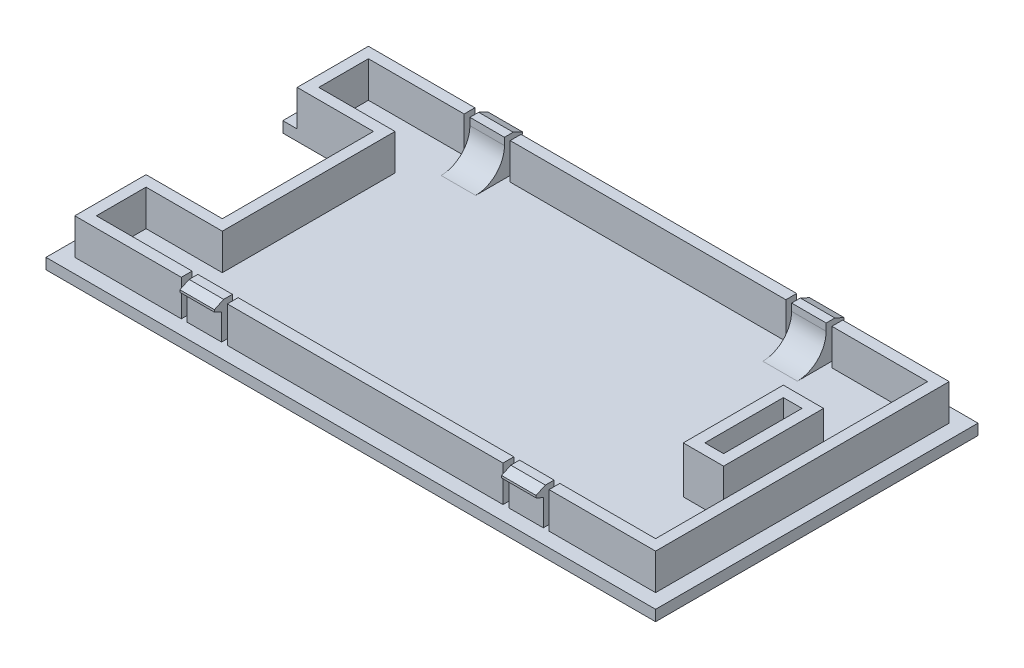
SolidWorks part; units mm, degrees
ref_plane "Front Plane" through (0, 0, 0) normal (0, 0, 1) x (1, 0, 0)
ref_plane "Top Plane" through (0, 0, 0) normal (0, 1, 0) x (1, 0, 0)
ref_plane "Right Plane" through (0, 0, 0) normal (1, 0, 0) x (0, 0, -1)
sketch "Sketch1" plane through (0, 0, 0) normal (0, 1, 0) x (1, 0, 0)
  line L0 (-42.35, 10.5) -> (-29.75, 10.5)
  line L1 (-42.35, -22.4) -> (42.35, -22.4)
  line L2 (-42.35, -22.4) -> (-42.35, -10.5)
  line L3 (-42.35, 22.4) -> (42.35, 22.4)
  line L4 (42.35, -22.4) -> (42.35, 22.4)
  line L5 (-42.35, -22.4) -> (42.35, 22.4) construction
  line L6 (-42.35, 22.4) -> (42.35, -22.4) construction
  line L7 (-29.75, 10.5) -> (-29.75, -10.5)
  line L8 (-29.75, -10.5) -> (-42.35, -10.5)
  line L9 (-42.35, 10.5) -> (-42.35, 22.4)
  point P0 (0, 0)
  dimension "D1" = 84.7
  dimension "D2" = 44.8
  dimension "D3" = 10.5
  dimension "D4" = 10.5
  dimension "D5" = 12.6
extrude "Boss-Extrude1" add sketch "Sketch1" along normal blind 2
sketch "Sketch2" plane through (0, 2, 0) normal (0, 1, 0) x (1, 0, 0)
  line L5 (-38.85, -12) -> (-38.85, -18.9)
  line L6 (-38.85, -18.9) -> (38.85, -18.9)
  line L7 (38.85, -18.9) -> (38.85, 18.9)
  line L8 (38.85, 18.9) -> (-38.85, 18.9)
  line L9 (-38.85, 18.9) -> (-38.85, 12)
  line L10 (-40.35, 20.4) -> (-40.35, 10.5)
  line L11 (-40.35, -10.5) -> (-40.35, -20.4)
  line L12 (-40.35, -20.4) -> (40.35, -20.4)
  line L13 (40.35, -20.4) -> (40.35, 20.4)
  line L14 (40.35, 20.4) -> (-40.35, 20.4)
  line L15 (-40.35, 20.4) -> (-40.35, 10.5)
  line L16 (-40.35, -10.5) -> (-40.35, -20.4)
  line L17 (-40.35, -20.4) -> (40.35, -20.4)
  line L18 (40.35, -20.4) -> (40.35, 20.4)
  line L19 (40.35, 20.4) -> (-40.35, 20.4)
  line L20 (-40.35, 10.5) -> (-29.75, 10.5)
  line L21 (-29.75, 10.5) -> (-29.75, -10.5)
  line L22 (-29.75, -10.5) -> (-40.35, -10.5)
  line L23 (-38.85, 12) -> (-28.25, 12)
  line L24 (-28.25, 12) -> (-28.25, -12)
  line L25 (-28.25, -12) -> (-38.85, -12)
  line L26 (-38.85, 18.9) -> (-38.85, 10.5) construction
  line L27 (-38.85, -10.5) -> (-38.85, -18.9) construction
  dimension "D3" = 1.5
  dimension "D4" = 1.5
  dimension "D5" = 1.5
  dimension "D1" = 2
  dimension "D2" = 1.5
extrude "Boss-Extrude2" add sketch "Sketch2" along normal blind 5
sketch "Sketch3" plane through (0, 7, 0) normal (0, 1, 0) x (1, 0, 0)
  line L0 (0, 22.4) -> (0, -22.4) construction
  line L1 (42.35, 22.4) -> (-42.35, 22.4) construction
  line L2 (-42.35, -22.4) -> (42.35, -22.4) construction
  line L3 (40.35, 20.4) -> (-40.35, 20.4) construction
  line L4 (-24.75, 20.4) -> (-25.55, 20.4)
  line L5 (-24.75, 20.4) -> (-24.75, 18.9)
  line L6 (-24.75, 18.9) -> (-25.55, 18.9)
  line L7 (-25.55, 20.4) -> (-25.55, 18.9)
  line L8 (38.85, 18.9) -> (-38.85, 18.9) construction
  line L10 (-19.95, 20.4) -> (-19.15, 20.4)
  line L11 (-19.95, 20.4) -> (-19.95, 18.9)
  line L12 (-19.95, 18.9) -> (-19.15, 18.9)
  line L13 (-19.15, 20.4) -> (-19.15, 18.9)
  line L14 (-29.75, 0) -> (0, 0) construction
  line L15 (-29.75, 10.5) -> (-29.75, -10.5) construction
  line L16 (-19.15, -20.4) -> (-19.15, -18.9)
  line L17 (-19.95, -18.9) -> (-19.15, -18.9)
  line L18 (-19.95, -20.4) -> (-19.95, -18.9)
  line L19 (-19.95, -20.4) -> (-19.15, -20.4)
  line L20 (-25.55, -20.4) -> (-25.55, -18.9)
  line L21 (-24.75, -18.9) -> (-25.55, -18.9)
  line L22 (-24.75, -20.4) -> (-24.75, -18.9)
  line L23 (-24.75, -20.4) -> (-25.55, -20.4)
  line L24 (19.15, 20.4) -> (19.15, 18.9)
  line L25 (19.95, 18.9) -> (19.15, 18.9)
  line L26 (19.95, 20.4) -> (19.95, 18.9)
  line L27 (19.95, 20.4) -> (19.15, 20.4)
  line L28 (25.55, 20.4) -> (25.55, 18.9)
  line L29 (24.75, 18.9) -> (25.55, 18.9)
  line L30 (24.75, 20.4) -> (24.75, 18.9)
  line L31 (24.75, 20.4) -> (25.55, 20.4)
  line L32 (24.75, -20.4) -> (25.55, -20.4)
  line L33 (24.75, -20.4) -> (24.75, -18.9)
  line L34 (24.75, -18.9) -> (25.55, -18.9)
  line L35 (25.55, -20.4) -> (25.55, -18.9)
  line L36 (19.95, -20.4) -> (19.15, -20.4)
  line L37 (19.95, -20.4) -> (19.95, -18.9)
  line L38 (19.95, -18.9) -> (19.15, -18.9)
  line L39 (19.15, -20.4) -> (19.15, -18.9)
  line L40 (-24.75, 19.65) -> (-19.95, 19.65) construction
  line L41 (-40.35, 20.4) -> (-40.35, 10.5) construction
  point P51 (-22.35, 19.65)
  dimension "D1" = 18
  dimension "D2" = 0.8
  dimension "D3" = 0.8
  dimension "D4" = 4.8
extrude "Cut-Extrude1" cut sketch "Sketch3" against normal up to surface (5 mm away) up to face at (-16.775, 2, 0)
sketch "Sketch4" plane through (0, 0, 20.4) normal (0, 0, 1) x (1, 0, 0)
  line L0 (0, 0) -> (0, 7) construction
  line L1 (-42.35, 0) -> (42.35, 0) construction
  line L2 (-19.15, 7) -> (19.15, 7) construction
  line L3 (-19.95, 2) -> (-19.95, 7) construction
  line L4 (-24.75, 7) -> (-19.95, 7)
  line L5 (-24.75, 7) -> (-24.75, 5.5)
  line L6 (-24.75, 5.5) -> (-19.95, 5.5)
  line L7 (-19.95, 7) -> (-19.95, 5.5)
  line L8 (19.95, 7) -> (19.95, 5.5)
  line L9 (24.75, 5.5) -> (19.95, 5.5)
  line L10 (24.75, 7) -> (24.75, 5.5)
  line L11 (24.75, 7) -> (19.95, 7)
  dimension "D1" = 1.5
extrude "Boss-Extrude3" add sketch "Sketch4" along normal blind 1
mirror "Mirror1" about plane through (0, 0, 0) normal (0, 0, 1) of "Boss-Extrude3"
chamfer "Chamfer3" distance 0.6 angle 65 8 edges at (22.35, 5.5, -21.4) (22.35, 7, -21.4) (-22.35, 5.5, -21.4) (-22.35, 7, -21.4) (22.35, 5.5, 21.4) (22.35, 7, 21.4) (-22.35, 7, 21.4) (-22.35, 5.5, 21.4)
sketch "Sketch6" plane through (0, 2, 0) normal (0, 1, 0) x (1, 0, 0)
  line L0 (38.85, -18.9) -> (38.85, 18.9) construction
  line L1 (32.25, -5.45) -> (34.85, -5.45)
  line L2 (32.25, -5.45) -> (32.25, 5.45)
  line L3 (32.25, 5.45) -> (34.85, 5.45)
  line L4 (34.85, -5.45) -> (34.85, 5.45)
  line L5 (32.25, -5.45) -> (34.85, 5.45) construction
  line L6 (32.25, 5.45) -> (34.85, -5.45) construction
  point P0 (33.55, 0)
  point P7 (0, 0)
  dimension "D1" = 10.9
  dimension "D2" = 2.6
  dimension "D3" = 4
extrude "Cut-Extrude2" cut sketch "Sketch6" against normal through all
sketch "Sketch7" plane through (0, 2, 0) normal (0, 1, 0) x (1, 0, 0)
  line L0 (34.85, 5.45) -> (32.25, 5.45) construction
  line L1 (34.85, -5.45) -> (34.85, 5.45) construction
  line L2 (32.25, -5.45) -> (34.85, -5.45) construction
  line L3 (32.25, 5.45) -> (32.25, -5.45) construction
  line L4 (34.85, 5.45) -> (32.25, 5.45)
  line L5 (34.85, -5.45) -> (34.85, 5.45)
  line L6 (32.25, -5.45) -> (34.85, -5.45)
  line L7 (32.25, 5.45) -> (32.25, -5.45)
  line L8 (36.35, 6.95) -> (30.75, 6.95)
  line L9 (30.75, 6.95) -> (30.75, -6.95)
  line L10 (30.75, -6.95) -> (36.35, -6.95)
  line L11 (36.35, -6.95) -> (36.35, 6.95)
  dimension "D1" = 1.5
extrude "Boss-Extrude4" add sketch "Sketch7" along normal blind 6.5
chamfer "Chamfer6" distance 0.5 angle 45 8 edges at (42.35, 0, 0) (0, 0, -22.4) (-42.35, 0, -16.45) (-36.05, 0, -10.5) (-29.75, 0, 0) (-36.05, 0, 10.5) (0, 0, 22.4) (-42.35, 0, 16.45)
fillet "Fillet1" radius 4 4 edges at (22.35, 2, -18.9) (22.35, 2, 18.9) (-22.35, 2, 18.9) (-22.35, 2, -18.9)
